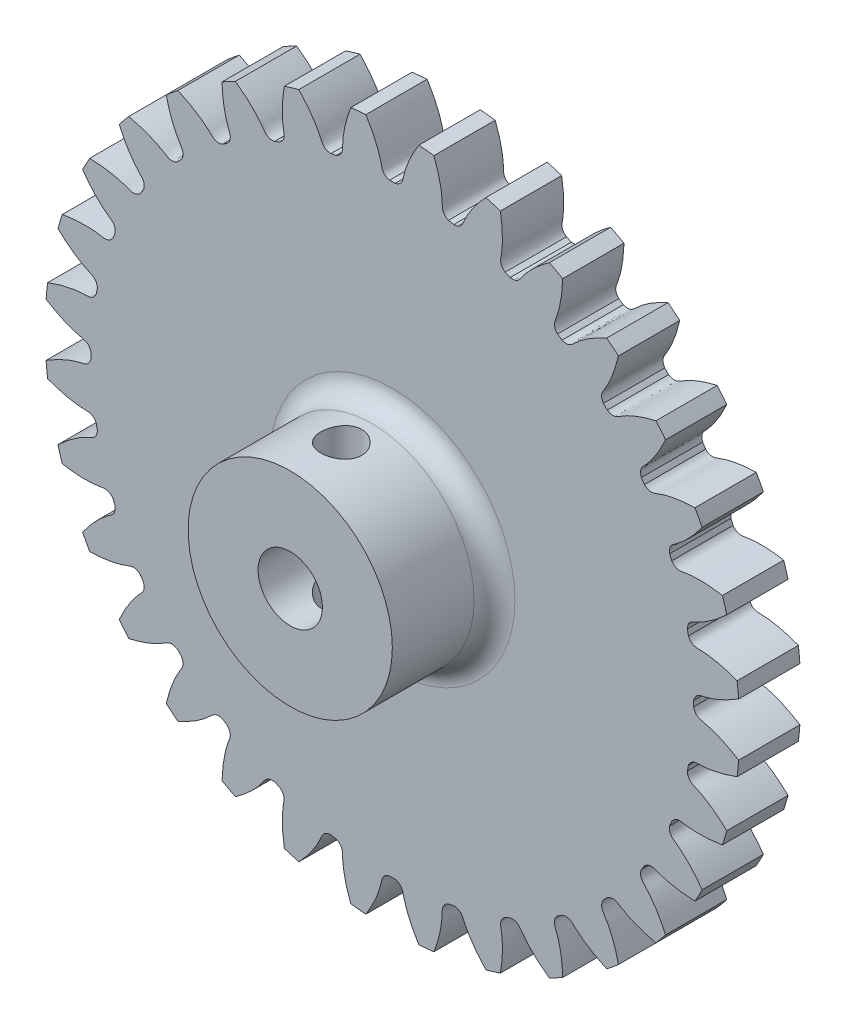
SolidWorks part; units mm, degrees
ref_plane "前视基准面" through (0, 0, 0) normal (0, 0, 1) x (1, 0, 0)
ref_plane "上视基准面" through (0, 0, 0) normal (0, 1, 0) x (1, 0, 0)
ref_plane "右视基准面" through (0, 0, 0) normal (1, 0, 0) x (0, 0, -1)
sketch "草图1" plane through (0, 0, 0) normal (0, 0, 1) x (1, 0, 0)
  circle A0 centre (0, 0) radius 17
extrude "凸台-拉伸1" add sketch "草图1" along normal blind 3
ref_axis "基准轴1" through (0, 0, -1.5) along (0, 0, 1)
sketch "草图2" plane through (0, 0, 0) normal (0, 0, 1) x (1, 0, 0)
  line L0 (0, 0) -> (0, 17) construction
  circle A0 centre (0, 0) radius 17 construction
  arc A1 (0.134, 14.7494) -> (-0.134, 14.7494) centre (0, 0) ccw
  arc A2 (3.353, 19.2696) -> (-3.353, 19.2696) centre (0, 0) ccw
  spline S0 degree 3 poles (0.134, 14.7494) (0.4888, 14.8352) (0.5084, 15.0924) (0.5734, 15.3608) (0.5904, 15.4254) (0.6103, 15.4954) (0.6333, 15.5708) (0.6597, 15.6514) (0.6897, 15.7371) (0.7235, 15.8279) (0.7613, 15.9235) (0.8034, 16.024) (0.8499, 16.129) (0.901, 16.2386) (0.957, 16.3525) (1.0179, 16.4707) (1.0841, 16.5928) (1.1557, 16.7189) (1.2329, 16.8487) (1.3158, 16.982) (1.4046, 17.1186) (1.4996, 17.2585) (1.6008, 17.4013) (1.7084, 17.5469) (1.8226, 17.6951) (1.9434, 17.8457) (2.0711, 17.9984) (2.2058, 18.1531) (2.3476, 18.3095) (2.4967, 18.4674) (2.653, 18.6266) (2.8169, 18.7869) (3.0483, 19.0044) (3.229, 19.1642) (3.353, 19.2696) knots 0 0 0 0 0.124533 0.135329 0.147193 0.160126 0.174128 0.189198 0.205337 0.222544 0.24082 0.260164 0.280577 0.302059 0.324609 0.348227 0.372914 0.39867 0.425494 0.453386 0.482348 0.512377 0.543476 0.575642 0.608878 0.643181 0.678554 0.714995 0.752504 0.791082 0.830729 0.871444 0.913227 1 1 1 1
  spline S1 degree 3 poles (-0.134, 14.7494) (-0.4888, 14.8352) (-0.5084, 15.0924) (-0.5734, 15.3608) (-0.5904, 15.4254) (-0.6103, 15.4954) (-0.6333, 15.5708) (-0.6597, 15.6514) (-0.6897, 15.7371) (-0.7235, 15.8279) (-0.7613, 15.9235) (-0.8034, 16.024) (-0.8499, 16.129) (-0.901, 16.2386) (-0.957, 16.3525) (-1.0179, 16.4707) (-1.0841, 16.5928) (-1.1557, 16.7189) (-1.2329, 16.8487) (-1.3158, 16.982) (-1.4046, 17.1186) (-1.4996, 17.2585) (-1.6008, 17.4013) (-1.7084, 17.5469) (-1.8226, 17.6951) (-1.9434, 17.8457) (-2.0711, 17.9984) (-2.2058, 18.1531) (-2.3476, 18.3095) (-2.4967, 18.4674) (-2.653, 18.6266) (-2.8169, 18.7869) (-3.0483, 19.0044) (-3.229, 19.1642) (-3.353, 19.2696) knots 0 0 0 0 0.124533 0.135329 0.147193 0.160126 0.174128 0.189198 0.205337 0.222544 0.24082 0.260164 0.280577 0.302059 0.324609 0.348227 0.372914 0.39867 0.425494 0.453386 0.482348 0.512377 0.543476 0.575642 0.608878 0.643181 0.678554 0.714995 0.752504 0.791082 0.830729 0.871444 0.913227 1 1 1 1
extrude "切除-拉伸1" cut sketch "草图2" along normal through all
pattern_circular "阵列(圆周)1" count 32 every 11.25 about axis through (0, 0, -1.5) along (0, 0, 1) of "切除-拉伸1"
sketch "草图3" plane through (0, 0, 0) normal (0, 0, 1) x (1, 0, 0)
  circle A0 centre (0, 0) radius 16 construction
  dimension "Dn" = 32
sketch "草图5" plane through (0, 0, 3) normal (0, 0, 1) x (1, 0, 0)
  circle A0 centre (0, 0) radius 5
  dimension "D1" = 10
extrude "凸台-拉伸2" add sketch "草图5" along normal blind 5
sketch "草图6" plane through (0, 0, 0) normal (0, 1, 0) x (1, 0, 0)
  line L0 (0, -8) -> (0, -5.5) construction
  line L1 (-5, -8) -> (5, -8) construction
  circle A0 centre (0, -5.5) radius 1
  dimension "D2" = 2
  dimension "D1" = 2.5
extrude "切除-拉伸3" cut sketch "草图6" against normal through all both and the other way through all
sketch "草图7" plane through (0, 0, 8) normal (0, 0, 1) x (1, 0, 0)
  circle A0 centre (0, 0) radius 1.575
  dimension "D1" = 3.15
extrude "切除-拉伸4" cut sketch "草图7" against normal through all both
fillet "圆角1" radius 1 1 edges at (5, 0, 3)
sketch "草图4" plane through (0, 0, 3) normal (0, 0, 1) x (1, 0, 0)
  circle A0 centre (0, 0) radius 1.575
  dimension "D1" = 3.15
